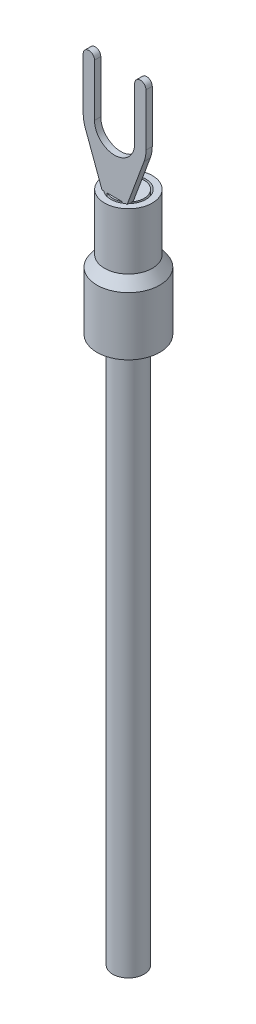
SolidWorks part; units mm, degrees
ref_plane "Front" through (0, 0, 0) normal (0, 0, 1) x (1, 0, 0)
ref_plane "Top" through (0, 0, 0) normal (0, 1, 0) x (1, 0, 0)
ref_plane "Right" through (0, 0, 0) normal (1, 0, 0) x (0, 0, -1)
sketch "草图1" plane through (0, 0, 0) normal (0, 0, 1) x (1, 0, 0)
  line L0 (0, 0) -> (0, 16.2439) construction
  line L1 (-2.3445, -0.8679) -> (-1, -4.5)
  line L3 (-1.6, 0) -> (-1.6, 4.6)
  line L4 (-1.6, 4.6) -> (-2.5, 4.6)
  line L5 (-2.5, 0) -> (-2.5, 4.6)
  line L6 (-1, -4.5) -> (0, -4.5) construction
  line L7 (0, -14.5) -> (0, -1.6)
  line L8 (-1, -4.5) -> (-1, -14.5)
  line L9 (-1, -14.5) -> (0, -14.5)
  arc A0 (-1.6, 0) -> (0, -1.6) centre (0, 0) ccw
  arc A1 (-2.5, 0) -> (-2.3445, -0.8679) centre (0, 0) ccw
  dimension "D1" = 3.2
  dimension "D2" = 5
  dimension "D3" = 9.1
  dimension "D4" = 4.5
  dimension "D5" = 1
  dimension "D6" = 10
extrude "凸台-拉伸1" add sketch "草图1" along normal blind 0.5
fillet "圆角1" 2 edges at (-1.6, 4.6, 0.25) (-2.5, 4.6, 0.25) type full round first side face at (-1.6, 2.3, 0.25) second side face at (-2.5, 2.3, 0.25) middle face at (-2.05, 4.6, 0.25)
chamfer "倒角1" distance 0.5 angle 45 1 edges at (-1, -9.5, 0.5)
mirror "镜向1" of "倒角1", "凸台-拉伸1", "圆角1"
sketch "草图3" plane through (0, 0, 0) normal (1, 0, 0) x (0, 0, -1)
  line L0 (0.6, -5.5679) -> (0.6, -16.934) construction
  line L1 (2.5, -4.5) -> (2.5, -9.004)
  line L2 (2.5, -9.004) -> (3.1, -9.8609)
  line L3 (3.1, -9.8609) -> (3.1, -14.5)
  line L4 (2.5, -4.5) -> (2, -4.5)
  line L5 (3.1, -14.5) -> (2.6, -14.5)
  line L6 (2, -4.5) -> (2, -9.1617)
  line L8 (2, -9.1617) -> (2.6, -10.0186)
  line L9 (2.6, -10.0186) -> (2.6, -14.5)
  line L10 (-0.5, -5.8507) -> (-0.5, -14.5) construction
  line L11 (2.5, -4.5) -> (1.8305, -4.5) construction
  line L12 (2, -5) -> (2, -9.1617) construction
  line L13 (3.1, -14.5) -> (2.7857, -14.5) construction
  line L14 (2.6, -10.0186) -> (2.6, -14.0357) construction
  line L15 (3.1, -14.5) -> (0.6, -14.5) construction
  line L17 (-1.3, -6.7472) -> (2.5, -6.7472) construction
  line L21 (2.6, -14.0357) -> (2.6, -14.0357) construction
  line L22 (2, -5) -> (1.8305, -5) construction
  line L24 (-0.5, -14.5) -> (0, -14.5) construction
  point P22 (0.6, -6.7472)
  dimension "D1" = 145
  dimension "D3" = 1.4
  dimension "D4" = 0.8
  dimension "D5" = 2.5
  dimension "D2" = 0.5
revolve "旋转1" add sketch "草图3" angle 360 about L0
sketch "草图5" plane through (0, -4.5, 0) normal (0, 1, 0) x (1, 0, 0)
  circle A1 centre (0, 0.6) radius 1.25
  dimension "D1" = 2.5
extrude "凸台-拉伸2" add sketch "草图5" against normal blind 53.5
